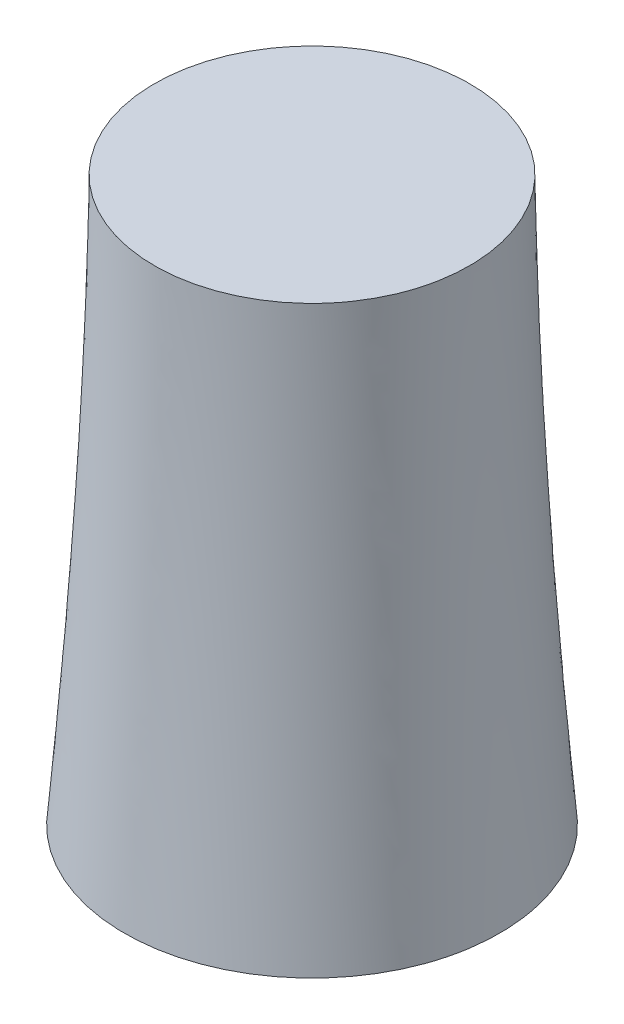
SolidWorks part; units mm, degrees
ref_plane "Front Plane" through (0, 0, 0) normal (0, 0, 1) x (1, 0, 0)
ref_plane "Top Plane" through (0, 0, 0) normal (0, 1, 0) x (1, 0, 0)
ref_plane "Right Plane" through (0, 0, 0) normal (1, 0, 0) x (0, 0, -1)
sketch "Sketch1" plane through (0, 0, 0) normal (0, 1, 0) x (1, 0, 0)
  circle A0 centre (0, 0) radius 25
  dimension "D1" = 50
ref_plane "Plane1" through (0, 75, 0) normal (0, 1, 0) x (1, 0, 0)
sketch "Sketch2" plane through (0, 75, 0) normal (0, 1, 0) x (1, 0, 0)
  circle A0 centre (0, 0) radius 21
  dimension "D1" = 42
loft "Loft1" add profiles "Sketch1", "Sketch2" connector at (-24.9993, 0, -0.191) connector at (-18.4446, 75, -10.0398)
sketch "Sketch3" plane through (0, 0, 0) normal (0, 0, 1) x (1, 0, 0)
  line L0 (-15.1539, 74.6686) -> (-15.1539, 71.5786)
  line L1 (-20.6539, 74.6686) -> (-15.6539, 74.6686)
  line L2 (-20.6539, 74.6686) -> (-20.6539, 71.5786)
  line L3 (-20.6539, 71.5786) -> (-15.6539, 71.5786)
  line L4 (-15.6539, 74.6686) -> (-15.6539, 71.5786)
  line L5 (-15.1539, 74.6686) -> (-10.1539, 74.6686)
  line L6 (-10.1539, 74.6686) -> (-10.1539, 71.5786)
  line L7 (-15.1539, 71.5786) -> (-10.1539, 71.5786)
  line L8 (-9.6539, 74.6686) -> (-9.6539, 71.5786)
  line L9 (-9.6539, 74.6686) -> (-4.6539, 74.6686)
  line L10 (-4.6539, 74.6686) -> (-4.6539, 71.5786)
  line L11 (-9.6539, 71.5786) -> (-4.6539, 71.5786)
  line L12 (-4.1539, 74.6686) -> (-4.1539, 71.5786)
  line L13 (-4.1539, 74.6686) -> (0.8461, 74.6686)
  line L14 (0.8461, 74.6686) -> (0.8461, 71.5786)
  line L15 (-4.1539, 71.5786) -> (0.8461, 71.5786)
  line L16 (1.3461, 74.6686) -> (1.3461, 71.5786)
  line L17 (1.3461, 74.6686) -> (6.3461, 74.6686)
  line L18 (6.3461, 74.6686) -> (6.3461, 71.5786)
  line L19 (1.3461, 71.5786) -> (6.3461, 71.5786)
  line L20 (6.8461, 74.6686) -> (6.8461, 71.5786)
  line L21 (6.8461, 74.6686) -> (11.8461, 74.6686)
  line L22 (11.8461, 74.6686) -> (11.8461, 71.5786)
  line L23 (6.8461, 71.5786) -> (11.8461, 71.5786)
  line L24 (12.3461, 74.6686) -> (12.3461, 71.5786)
  line L25 (12.3461, 74.6686) -> (17.3461, 74.6686)
  line L26 (17.3461, 74.6686) -> (17.3461, 71.5786)
  line L27 (12.3461, 71.5786) -> (17.3461, 71.5786)
  line L28 (17.8461, 74.6686) -> (17.8461, 71.5786)
  line L29 (17.8461, 74.6686) -> (22.8461, 74.6686)
  line L30 (22.8461, 74.6686) -> (22.8461, 71.5786)
  line L31 (17.8461, 71.5786) -> (22.8461, 71.5786)
  dimension "D1" = 5
  dimension "D2" = 3.09
  dimension "D3" = 8
